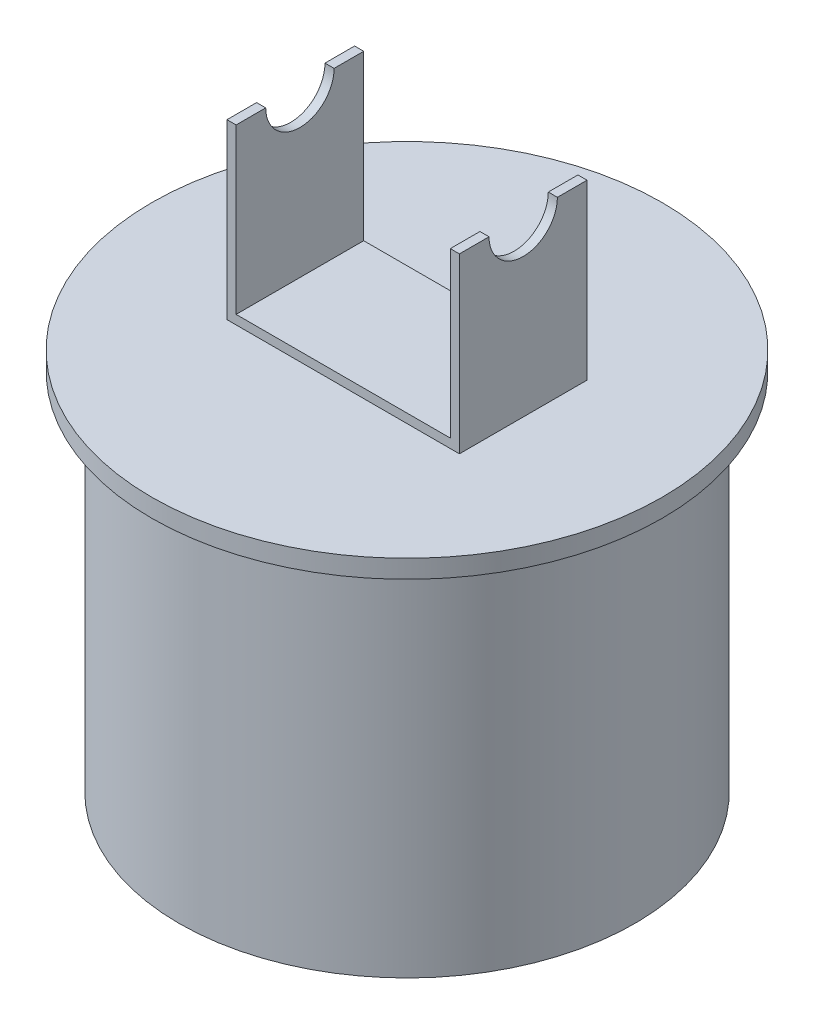
SolidWorks part; units mm, degrees
ref_plane "Front Plane" through (0, 0, 0) normal (0, 0, 1) x (1, 0, 0)
ref_plane "Top Plane" through (0, 0, 0) normal (0, 1, 0) x (1, 0, 0)
ref_plane "Right Plane" through (0, 0, 0) normal (1, 0, 0) x (0, 0, -1)
sketch "Sketch1" plane through (0, 0, 0) normal (0, 1, 0) x (1, 0, 0)
  circle A0 centre (0, 0) radius 56
  circle A1 centre (0, 0) radius 50
  dimension "D1" = 100
  dimension "D2" = 112
extrude "Boss-Extrude1" add sketch "Sketch1" against normal blind 80 contours A1
extrude "Boss-Extrude2" add sketch "Sketch1<3>" along normal blind 4 contours A1 | A0 A1 region at (-54.4161, 0, 0) region at (0, 0, 0)
sketch "Sketch1<3>" plane through (0, 0, 0) normal (0, 1, 0) x (1, 0, 0) same geometry as "Sketch1"
sketch "Sketch5" plane through (0, 4, 0) normal (0, 1, 0) x (1, 0, 0)
  line L1 (-25.5, 14) -> (25.5, 14)
  line L2 (-25.5, 14) -> (-25.5, -14)
  line L3 (-25.5, -14) -> (25.5, -14)
  line L4 (25.5, 14) -> (25.5, -14)
  line L5 (-25.5, 14) -> (25.5, -14) construction
  line L6 (-25.5, -14) -> (25.5, 14) construction
  point P0 (0, 0)
  dimension "D1" = 51
  dimension "D2" = 28
extrude "Boss-Extrude4" add sketch "Sketch5" along normal blind 38
sketch "Sketch6" plane through (0, 42, 0) normal (0, 1, 0) x (1, 0, 0)
  line L5 (-23.5, 14) -> (23.5, 14)
  line L6 (-23.5, 14) -> (-23.5, -14)
  line L7 (-23.5, -14) -> (23.5, -14)
  line L8 (23.5, 14) -> (23.5, -14)
  line L9 (-23.5, 14) -> (23.5, -14) construction
  line L10 (-23.5, -14) -> (23.5, 14) construction
  point P0 (0, 0)
  dimension "D1" = 47
  dimension "D2" = 28
extrude "Cut-Extrude2" cut sketch "Sketch6" against normal blind 36
ref_point "Point1"
sketch "Sketch8" plane through (25.5, 0, 0) normal (1, 0, 0) x (0, 0, -1)
  circle A0 centre (0, 42) radius 7.5
  dimension "D1" = 15
extrude "Cut-Extrude3" cut sketch "Sketch8" against normal blind 51
ref_point "Point2"
ref_point "Point3"
ref_plane "Plane3" through (0, 42, 0) normal (0, 1, 0) x (1, 0, 0)
sketch "Sketch9" plane through (0, 42, 0) normal (0, 1, 0) x (1, 0, 0)
  line L0 (-25.5, 0) -> (25.5, 0)
  point P4 (0, 0)
